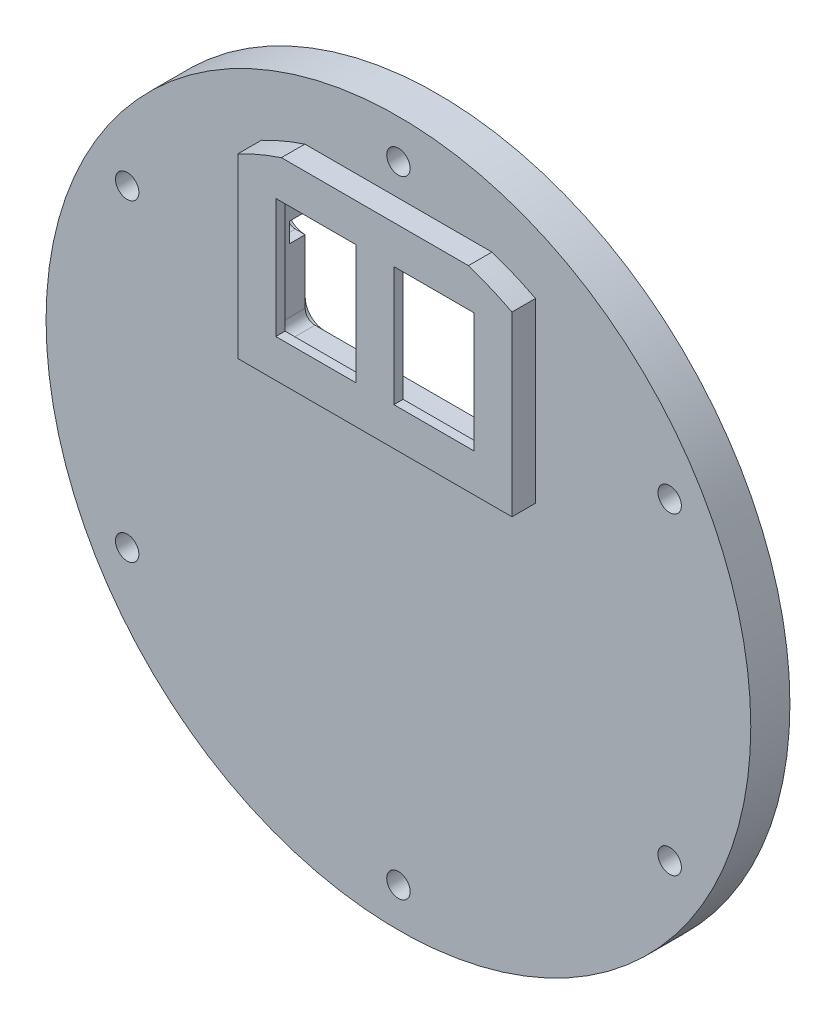
SolidWorks part; units mm, degrees
ref_plane "Front Plane" through (0, 0, 0) normal (0, 0, 1) x (1, 0, 0)
ref_plane "Top Plane" through (0, 0, 0) normal (0, 1, 0) x (1, 0, 0)
ref_plane "Right Plane" through (0, 0, 0) normal (1, 0, 0) x (0, 0, -1)
sketch "Sketch1" plane through (0, 0, 0) normal (0, 0, 1) x (1, 0, 0)
  circle A0 centre (0, 0) radius 57.15
  dimension "D1" = 114.3
extrude "Boss-Extrude1" add sketch "Sketch1" along normal blind 6.35
sketch "Sketch2" plane through (0, 0, 6.35) normal (0, 0, 1) x (1, 0, 0)
  line L0 (22.225, 13.9303) -> (22.225, 45.6803)
  line L1 (-22.225, 45.6803) -> (22.225, 45.6803)
  line L2 (-22.225, 45.6803) -> (-22.225, 13.9303)
  line L3 (-22.225, 13.9303) -> (22.225, 13.9303)
  line L9 (0, 13.9303) -> (0, 45.6803) construction
  line L10 (0, 0) -> (0, 57.15) construction
  circle A1 centre (0, 0) radius 57.15 construction
  circle A2 centre (0, 0) radius 50.8 construction
  dimension "D3" = 6.35
  dimension "D1" = 44.45
  dimension "D2" = 31.75
extrude "Boss-Extrude2" add sketch "Sketch2" along normal blind 3.81 contours L1 L0 L3 L2
sketch "Sketch3" plane through (0, 0, 10.16) normal (0, 0, 1) x (1, 0, 0)
  line L0 (0, 45.6803) -> (0, 13.9303) construction
  line L1 (-16.075, 39.5053) -> (-3.075, 39.5053)
  line L2 (-16.075, 39.5053) -> (-16.075, 20.1053)
  line L3 (-16.075, 20.1053) -> (-3.075, 20.1053)
  line L4 (-3.075, 39.5053) -> (-3.075, 20.1053)
  line L5 (3.075, 39.5053) -> (16.075, 39.5053)
  line L6 (3.075, 39.5053) -> (3.075, 20.1053)
  line L7 (3.075, 20.1053) -> (16.075, 20.1053)
  line L8 (16.075, 39.5053) -> (16.075, 20.1053)
  line L9 (-22.225, 45.6803) -> (22.225, 45.6803) construction
  line L10 (-22.225, 13.9303) -> (22.225, 13.9303) construction
  line L11 (-22.225, 29.8053) -> (-16.075, 29.8053) construction
  line L12 (-22.225, 45.6803) -> (-22.225, 13.9303) construction
  line L13 (16.075, 29.8053) -> (22.225, 29.8053) construction
  line L14 (22.225, 13.9303) -> (22.225, 45.6803) construction
  line L15 (-3.075, 29.8053) -> (3.075, 29.8053) construction
  dimension "D1" = 19.4
  dimension "D2" = 13
  dimension "D3" = 13
  dimension "D4" = 19.4
extrude "Cut-Extrude1" cut sketch "Sketch3" against normal through all
sketch "Sketch4" plane through (0, 0, 0) normal (0, 0, -1) x (-1, 0, 0)
  line L0 (16.075, 20.1053) -> (3.075, 20.1053) construction
  line L1 (-19.885, 43.3153) -> (19.885, 43.3153)
  line L2 (-19.885, 43.3153) -> (-19.885, 16.2953)
  line L3 (-19.885, 16.2953) -> (19.885, 16.2953)
  line L4 (19.885, 43.3153) -> (19.885, 16.2953)
  line L5 (3.075, 39.5053) -> (16.075, 39.5053) construction
  line L6 (16.075, 39.5053) -> (16.075, 20.1053) construction
  line L7 (-16.075, 20.1053) -> (-16.075, 39.5053) construction
  dimension "D1" = 3.81
  dimension "D2" = 3.81
  dimension "D3" = 3.81
  dimension "D4" = 3.81
extrude "Cut-Extrude2" cut sketch "Sketch4" against normal offset from surface (8.66 mm away) 1.5 up to face at (-9.575, 29.8053, 10.16)
fillet "Fillet1" radius 1.5875 4 edges at (19.885, 16.2953, 4.33) (-19.885, 16.2953, 4.33) (-19.885, 43.3153, 4.33) (19.885, 43.3153, 4.33)
sketch "Sketch8" plane through (0, 0, 0) normal (0, 0, -1) x (-1, 0, 0)
  line L0 (-19.885, 41.7278) -> (-19.885, 17.8828) construction
  line L1 (-18.2975, 16.2953) -> (18.2975, 16.2953) construction
  line L2 (19.885, 17.8828) -> (19.885, 41.7278) construction
  line L3 (18.2975, 43.3153) -> (-18.2975, 43.3153) construction
  line L4 (-19.885, 41.7278) -> (-19.885, 17.8828)
  line L5 (-18.2975, 16.2953) -> (18.2975, 16.2953)
  line L6 (19.885, 17.8828) -> (19.885, 41.7278)
  line L7 (18.2975, 43.3153) -> (-18.2975, 43.3153)
  line L8 (18.2975, 44.9028) -> (-18.2975, 44.9028)
  line L9 (-21.4725, 41.7278) -> (-21.4725, 17.8828) construction
  line L10 (-18.2975, 14.7078) -> (18.2975, 14.7078)
  line L11 (21.4725, 17.8828) -> (21.4725, 41.7278) construction
  line L12 (-21.4725, 32.9803) -> (-21.4725, 41.7278)
  line L13 (-21.4725, 26.6303) -> (-21.4725, 17.8828)
  line L14 (21.4725, 17.8828) -> (21.4725, 26.6303)
  line L15 (21.4725, 32.9803) -> (21.4725, 41.7278)
  arc A0 (-18.2975, 43.3153) -> (-19.885, 41.7278) centre (-18.2975, 41.7278) ccw construction
  circle A1 centre (0, 0) radius 57.15
  circle A2 centre (0, 0) radius 57.15
  arc A3 (-19.885, 17.8828) -> (-18.2975, 16.2953) centre (-18.2975, 17.8828) ccw construction
  arc A4 (18.2975, 16.2953) -> (19.885, 17.8828) centre (18.2975, 17.8828) ccw construction
  arc A5 (19.885, 41.7278) -> (18.2975, 43.3153) centre (18.2975, 41.7278) ccw construction
  arc A6 (-18.2975, 43.3153) -> (-19.885, 41.7278) centre (-18.2975, 41.7278) ccw
  arc A7 (-19.885, 17.8828) -> (-18.2975, 16.2953) centre (-18.2975, 17.8828) ccw
  arc A8 (18.2975, 16.2953) -> (19.885, 17.8828) centre (18.2975, 17.8828) ccw
  arc A9 (19.885, 41.7278) -> (18.2975, 43.3153) centre (18.2975, 41.7278) ccw
  arc A10 (-18.2975, 44.9028) -> (-21.4725, 41.7278) centre (-18.2975, 41.7278) ccw
  arc A11 (-21.4725, 17.8828) -> (-18.2975, 14.7078) centre (-18.2975, 17.8828) ccw
  arc A12 (18.2975, 14.7078) -> (21.4725, 17.8828) centre (18.2975, 17.8828) ccw
  arc A13 (21.4725, 41.7278) -> (18.2975, 44.9028) centre (18.2975, 41.7278) ccw
  arc A14 (21.4725, 26.6303) -> (21.4725, 32.9803) centre (21.4725, 29.8053) ccw
  arc A15 (-21.4725, 32.9803) -> (-21.4725, 26.6303) centre (-21.4725, 29.8053) ccw
  dimension "D3" = 6.35
  dimension "D4" = 6.35
  dimension "D1" = 0
  dimension "D2" = 1.5875
extrude "Cut-Extrude3" cut sketch "Sketch8" against normal blind 1.5875 contours L12 A10 L8 A13 L15 A14 L14 A12 L10 A11 L13 A15
hole_wizard "CBORE for #6 Pan Head Machine Screw1" positions "Sketch9" profile "Sketch10" counterbore size "#6" standard "ANSI Inch" end condition through all
sketch "Sketch9" plane through (0, 0, 0) normal (0, 0, -1) x (-1, 0, 0)
  line L0 (0, 0) -> (-43.9941, -25.4) construction
  line L2 (-43.9941, -25.4) -> (-49.4934, -28.575) construction
  line L3 (0, 0) -> (-57.15, 0) construction
  circle A1 centre (0, 0) radius 57.15 construction
  point P0 (-43.9941, -25.4)
  dimension "D1" = 50.8
  dimension "D2" = 30
sketch "Sketch10" plane through (43.9941, -25.4, 0) normal (1, 0, 0) x (0, 1, 0)
  line L0 (0, 0) -> (0, 10.16)
  line L1 (0, 10.16) -> (1.8986, 10.16)
  line L3 (1.8986, 10.16) -> (1.8987, 2.4638)
  line L4 (1.8987, 2.4638) -> (3.7706, 2.4638)
  line L5 (3.7706, 2.4638) -> (3.7706, 0)
  line L7 (3.7706, 0) -> (0, 0)
  line L11 (0, -6.35) -> (0, 107.95) construction
  dimension "Thru Hole Dia." = 3.7973
  dimension "Thru Hole Depth" = 10.16
  dimension "C'Bore Dia." = 7.5413
  dimension "C'Bore Depth" = 2.4638
pattern_circular "CirPattern1" count 6 over 360 about axis through (0, 0, 6.35) along (0, 0, -1) of "CBORE for #6 Pan Head Machine Screw1" reverse direction yes
sketch "Sketch27" plane through (0, 0, 6.35) normal (0, 0, 1) x (1, 0, 0)
  circle A0 centre (0, 0) radius 48.133
  circle A1 centre (0, 0) radius 63.5
  dimension "D1" = 96.266
  dimension "D2" = 127
extrude "Cut-Extrude14" cut sketch "Sketch27" along normal through all
sketch "Sketch28" plane through (0, 0, 1.5875) normal (0, 0, -1) x (-1, 0, 0)
  line L0 (-21.4725, 31.3928) -> (-19.885, 31.3928)
  line L1 (-19.885, 17.8828) -> (-19.885, 41.7278) construction
  line L2 (-21.4725, 28.2178) -> (-19.885, 28.2178)
  line L4 (-19.885, 31.3928) -> (-19.885, 28.2178)
  line L5 (21.4725, 28.2178) -> (19.885, 28.2178)
  line L6 (21.4725, 31.3928) -> (19.885, 31.3928)
  line L7 (19.885, 41.7278) -> (19.885, 17.8828) construction
  line L8 (19.885, 31.3928) -> (19.885, 28.2178)
  arc A0 (-21.4725, 31.3928) -> (-21.4725, 28.2178) centre (-21.4725, 29.8053) ccw
  arc A1 (21.4725, 28.2178) -> (21.4725, 31.3928) centre (21.4725, 29.8053) ccw
  dimension "D1" = 3.175
extrude "Cut-Extrude15" cut sketch "Sketch28" against normal blind 2.54
sketch "Sketch29" plane through (0, 0, 0) normal (0, 0, -1) x (-1, 0, 0)
  line L0 (21.4725, 32.9803) -> (21.4725, 41.7278) construction
  line L1 (21.4725, 17.8828) -> (21.4725, 26.6303) construction
  line L2 (-18.2975, 14.7078) -> (18.2975, 14.7078) construction
  line L3 (-21.4725, 26.6303) -> (-21.4725, 17.8828) construction
  line L4 (-21.4725, 32.9803) -> (-21.4725, 41.7278) construction
  line L5 (18.2975, 44.9028) -> (-18.2975, 44.9028) construction
  line L6 (21.4725, 32.9803) -> (21.4725, 41.7278)
  line L7 (21.4725, 17.8828) -> (21.4725, 26.6303)
  line L8 (-18.2975, 14.7078) -> (18.2975, 14.7078)
  line L9 (-21.4725, 26.6303) -> (-21.4725, 17.8828)
  line L10 (-21.4725, 32.9803) -> (-21.4725, 41.7278)
  line L11 (18.2975, 44.9028) -> (-18.2975, 44.9028)
  arc A0 (21.4725, 41.7278) -> (18.2975, 44.9028) centre (18.2975, 41.7278) ccw construction
  arc A1 (21.4725, 26.6303) -> (21.4725, 32.9803) centre (21.4725, 29.8053) ccw construction
  arc A2 (18.2975, 14.7078) -> (21.4725, 17.8828) centre (18.2975, 17.8828) ccw construction
  arc A3 (-21.4725, 17.8828) -> (-18.2975, 14.7078) centre (-18.2975, 17.8828) ccw construction
  arc A4 (-21.4725, 32.9803) -> (-21.4725, 26.6303) centre (-21.4725, 29.8053) ccw construction
  arc A5 (-18.2975, 44.9028) -> (-21.4725, 41.7278) centre (-18.2975, 41.7278) ccw construction
  arc A6 (21.4725, 41.7278) -> (18.2975, 44.9028) centre (18.2975, 41.7278) ccw
  arc A7 (21.4725, 26.6303) -> (21.4725, 32.9803) centre (21.4725, 29.8053) ccw
  arc A8 (18.2975, 14.7078) -> (21.4725, 17.8828) centre (18.2975, 17.8828) ccw
  arc A9 (-21.4725, 17.8828) -> (-18.2975, 14.7078) centre (-18.2975, 17.8828) ccw
  arc A10 (-21.4725, 32.9803) -> (-21.4725, 26.6303) centre (-21.4725, 29.8053) ccw
  arc A11 (-18.2975, 44.9028) -> (-21.4725, 41.7278) centre (-18.2975, 41.7278) ccw
sketch "Sketch30" plane through (0, 0, 0) normal (0, 0, -1) x (-1, 0, 0)
  line L0 (-18.2975, 16.2953) -> (18.2975, 16.2953) construction
  line L1 (19.885, 17.8828) -> (19.885, 41.7278) construction
  line L2 (19.885, 41.7278) -> (19.885, 31.3928) construction
  line L3 (-18.2975, 43.3153) -> (18.2975, 43.3153) construction
  line L4 (-19.885, 41.7278) -> (-19.885, 17.8828) construction
  line L5 (-18.2975, 16.2953) -> (18.2975, 16.2953)
  line L6 (19.885, 17.8828) -> (19.885, 41.7278)
  line L7 (19.885, 41.7278) -> (19.885, 31.3928)
  line L8 (-18.2975, 43.3153) -> (18.2975, 43.3153)
  line L9 (-19.885, 41.7278) -> (-19.885, 17.8828)
  circle A1 centre (0, 0) radius 57.15
  circle A2 centre (0, 0) radius 57.15
  arc A3 (-19.885, 17.8828) -> (-18.2975, 16.2953) centre (-18.2975, 17.8828) ccw construction
  arc A4 (18.2975, 16.2953) -> (19.885, 17.8828) centre (18.2975, 17.8828) ccw construction
  arc A5 (19.885, 41.7278) -> (18.2975, 43.3153) centre (18.2975, 41.7278) ccw construction
  arc A6 (-18.2975, 43.3153) -> (-19.885, 41.7278) centre (-18.2975, 41.7278) ccw construction
  arc A7 (-19.885, 17.8828) -> (-18.2975, 16.2953) centre (-18.2975, 17.8828) ccw
  arc A8 (18.2975, 16.2953) -> (19.885, 17.8828) centre (18.2975, 17.8828) ccw
  arc A9 (19.885, 41.7278) -> (18.2975, 43.3153) centre (18.2975, 41.7278) ccw
  arc A10 (-18.2975, 43.3153) -> (-19.885, 41.7278) centre (-18.2975, 41.7278) ccw
  dimension "D1" = 0
